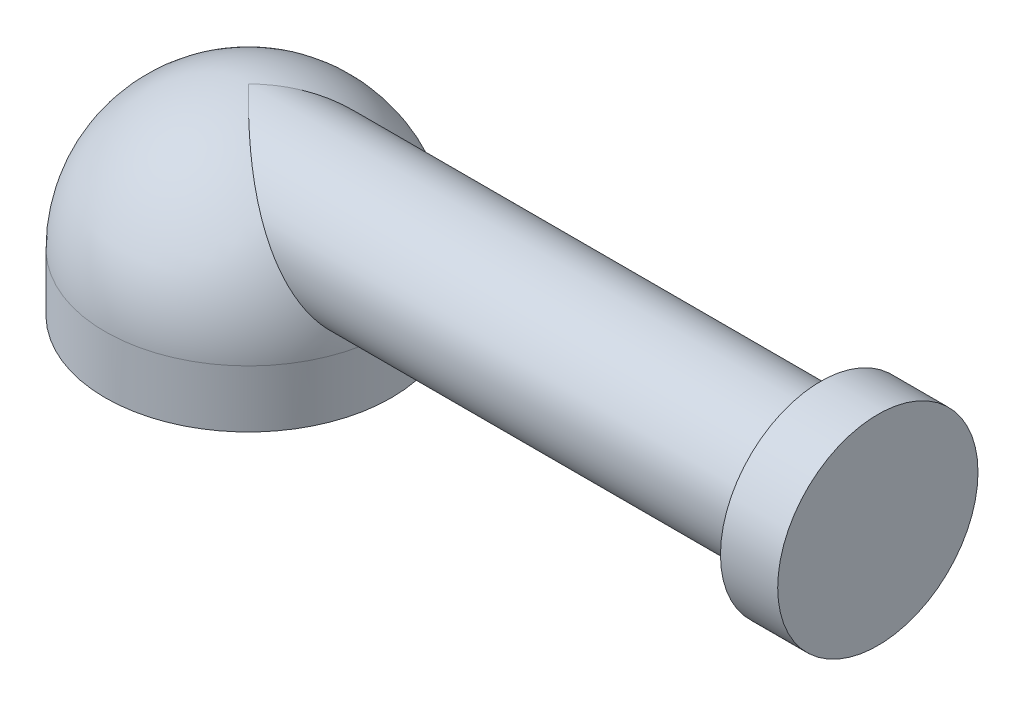
SolidWorks part; units mm, degrees
ref_plane "前视基准面" through (0, 0, 0) normal (0, 0, 1) x (1, 0, 0)
ref_plane "上视基准面" through (0, 0, 0) normal (0, 1, 0) x (1, 0, 0)
ref_plane "右视基准面" through (0, 0, 0) normal (1, 0, 0) x (0, 0, -1)
other "Configuration Table"
sketch "草图1" plane through (0, 0, 0) normal (0, 1, 0) x (1, 0, 0)
  circle A1 centre (0, 0) radius 2
  circle A2 centre (0, 0) radius 2.5
extrude "凸台-拉伸1" add sketch "草图1" along normal blind 1
sketch "草图2" plane through (0, 0, 0) normal (0, 0, 1) x (1, 0, 0)
  line L0 (0, 0) -> (0, 1)
  line L1 (2, 1) -> (-2, 1) construction
  line L2 (0, 1) -> (0, 3.5)
  line L3 (0, 1) -> (2.5, 1)
  arc A0 (2.5, 1) -> (0, 3.5) centre (0, 1) ccw
ref_axis "基准轴1" through (0, 0, 0) along (0, 1, 0)
revolve "旋转1" add sketch "草图2" angle 360 about L2 region at (1.061, 2.061, 0)
sketch "草图3" plane through (0, 0, 0) normal (1, 0, 0) x (0, 0, -1)
  line L0 (0, 1) -> (0, 3.5)
  line L1 (-2.5, 1) -> (2.5, 1) construction
  arc A0 (2.5, 1) -> (-2.5, 1) centre (0, 1) ccw construction
  circle A1 centre (0, 2.25) radius 1.25
extrude "凸台-拉伸2" add sketch "草图3" along normal blind 10 contours L0 A1 | A1 region at (0, 2.25, -0.5305)
ref_plane "基准面1" through (10, 0, 0) normal (1, 0, 0) x (0, 0, -1)
sketch "草图4" plane through (10, 0, 0) normal (1, 0, 0) x (0, 0, -1)
  circle A0 centre (0, 2.25) radius 1.75
extrude "凸台-拉伸3" add sketch "草图4" along normal blind 1
